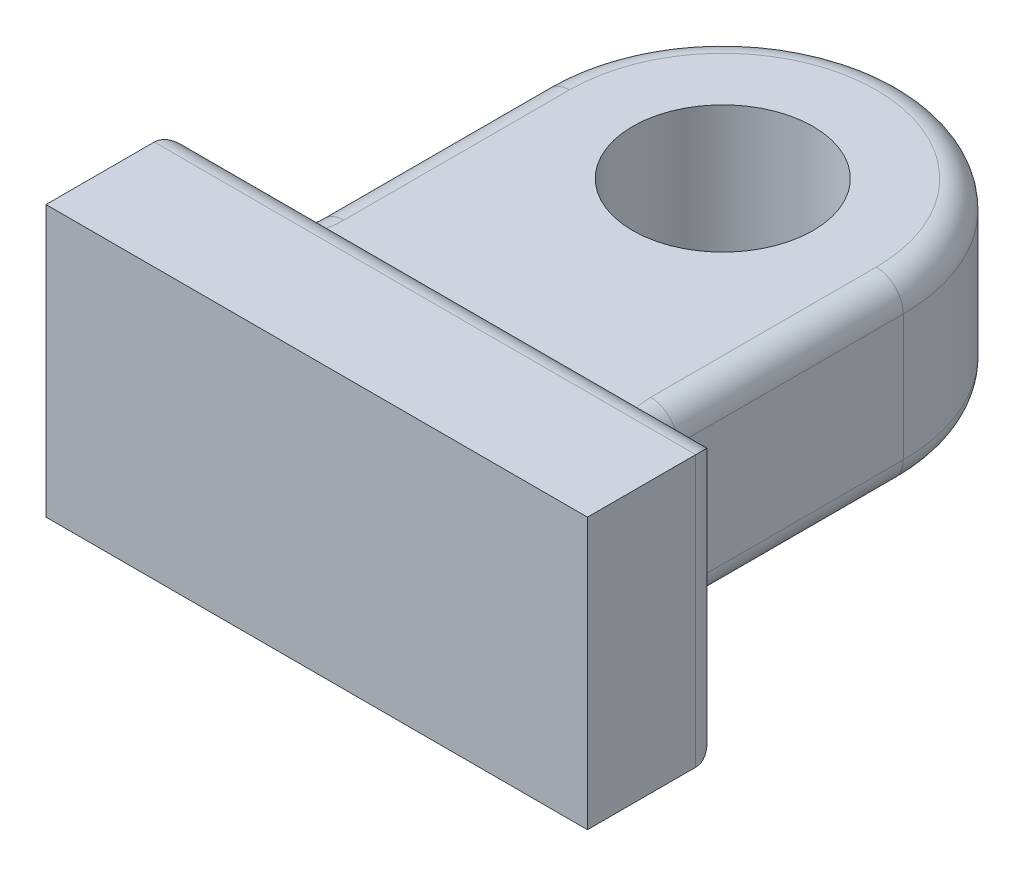
SolidWorks part; units mm, degrees
material "Plain Carbon Steel"
ref_plane "Front Plane" through (0, 0, 0) normal (0, 0, 1) x (1, 0, 0)
ref_plane "Top Plane" through (0, 0, 0) normal (0, 1, 0) x (1, 0, 0)
ref_plane "Right Plane" through (0, 0, 0) normal (1, 0, 0) x (0, 0, -1)
sketch "Sketch1" plane through (0, 0, 0) normal (0, 0, 1) x (1, 0, 0)
  line L1 (-30, 15) -> (30, 15)
  line L2 (-30, 15) -> (-30, -15)
  line L3 (-30, -15) -> (30, -15)
  line L4 (30, 15) -> (30, -15)
  line L5 (-30, 15) -> (30, -15) construction
  line L6 (-30, -15) -> (30, 15) construction
  point P0 (0, 0)
  dimension "D1" = 60
  dimension "D2" = 30
extrude "Boss-Extrude1" add sketch "Sketch1" along normal blind 15
sketch "Sketch2" plane through (0, 0, 0) normal (0, 1, 0) x (1, 0, 0)
  line L0 (-20, 30) -> (-20, 0)
  line L1 (30, 0) -> (-30, 0) construction
  line L2 (-20, 0) -> (20, 0)
  line L3 (20, 0) -> (20, 30)
  line L4 (30, -15) -> (30, 0) construction
  circle A0 centre (0, 30) radius 10
  arc A1 (20, 30) -> (-20, 30) centre (0, 30) ccw
  dimension "D1" = 40
  dimension "D2" = 20
  dimension "D3" = 10
  dimension "D4" = 30
extrude "Boss-Extrude2" add sketch "Sketch2" along normal mid plane 20
fillet "Fillet1" radius 5 2 edges at (20, 0, 0) (-20, 0, 0)
fillet "Fillet2" radius 3 14 edges at (21.4645, 10, -1.4645) (20, 10, -17.5) (-21.4645, 10, -1.4645) (-20, 10, -17.5) (21.4645, -10, -1.4645) (20, -10, -17.5) (-21.4645, -10, -1.4645) (-20, -10, -17.5) (0, 10, -50) (0, -10, -50) (0, -15, 0) (30, 0, 0) (0, 15, 0) (-30, 0, 0)
